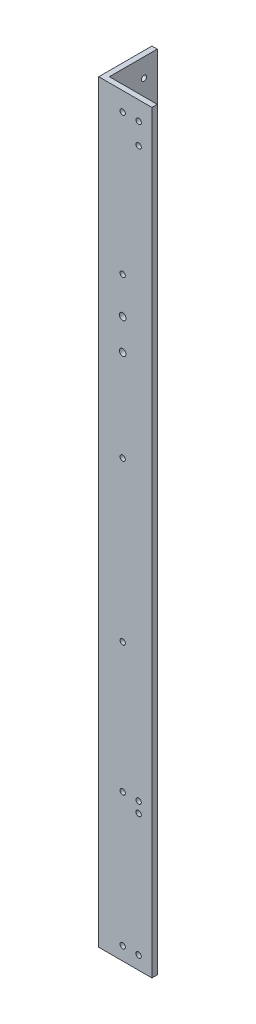
SolidWorks part; units mm, degrees
ref_plane "Front Plane" through (0, 0, 0) normal (0, 0, 1) x (1, 0, 0)
ref_plane "Top Plane" through (0, 0, 0) normal (0, 1, 0) x (1, 0, 0)
ref_plane "Right Plane" through (0, 0, 0) normal (1, 0, 0) x (0, 0, -1)
sketch "Sketch2" plane through (0, 0, 0) normal (0, 1, 0) x (1, 0, 0)
  line L0 (0, 31.75) -> (3.175, 31.75)
  line L1 (3.175, 31.75) -> (3.175, 3.175)
  line L2 (3.175, 3.175) -> (31.75, 3.175)
  line L3 (31.75, 3.175) -> (31.75, 0)
  line L4 (31.75, 0) -> (0, 0)
  line L5 (0, 0) -> (0, 31.75)
  point P9 (1.5875, 31.75)
  point P10 (31.75, 1.5875)
  dimension "D4" = 3.175
  dimension "D1" = 31.75
  dimension "D2" = 31.75
  dimension "D3" = 3.175
extrude "Boss-Extrude1" add sketch "Sketch2" along normal blind 450
sketch "FrontSideHoles-Sketch3" plane through (0, 0, 0) normal (0, 0, 1) x (1, 0, 0)
  line L0 (0, 0) -> (31.75, 0) construction
  line L1 (0, 450) -> (0, 0) construction
  circle A1 centre (23.8125, 81.1125) radius 1.5875
  circle A2 centre (14.2875, 87.4625) radius 1.5875
  circle A3 centre (23.8125, 87.4625) radius 1.5875
  circle A4 centre (14.2875, 438.8875) radius 1.5875
  circle A6 centre (23.8125, 438.8875) radius 1.5875
  circle A7 centre (23.8125, 426.1875) radius 1.5875
  circle A8 centre (14.2875, 333.1776) radius 2
  circle A9 centre (14.2875, 314.6526) radius 2
  circle A10 centre (14.2875, 260) radius 1.5875
  circle A11 centre (14.2875, 165) radius 1.5875
  circle A12 centre (14.2875, 355) radius 1.5875
  circle A13 centre (14.2875, 7.9375) radius 1.5875
  circle A14 centre (23.8125, 7.9375) radius 1.5875
  dimension "D4" = 3.175
  dimension "D15" = 4
  dimension "D8" = 11.1125
  dimension "D11" = 18.525
  dimension "D9" = 314.6526
  dimension "D6" = 165
  dimension "D10" = 95
  dimension "D13" = 95
  dimension "D12" = 7.9375
  dimension "D3" = 9.525
  dimension "D2" = 14.2875
  dimension "D5" = 6.35
  dimension "D14" = 81.1125
  dimension "D7" = 12.7
sketch "LeftSideHoles-Sketch4" plane through (0, 0, 0) normal (-1, 0, 0) x (0, 0, 1)
  line L0 (-31.75, 450) -> (0, 450) construction
  line L1 (0, 450) -> (0, 0) construction
  line L3 (-31.75, 0) -> (0, 0) construction
  circle A0 centre (-23.8125, 81.1125) radius 1.5875
  circle A1 centre (-14.2875, 81.1125) radius 1.5875
  circle A2 centre (-23.8125, 87.4625) radius 1.5875
  circle A4 centre (-23.8125, 438.8875) radius 1.5875
  circle A6 centre (-23.8125, 426.1875) radius 1.5875
  circle A7 centre (-14.2875, 426.1875) radius 1.5875
  circle A8 centre (-23.8125, 327.6026) radius 1.5875
  circle A9 centre (-14.2875, 327.6026) radius 1.5875
  circle A10 centre (-23.8125, 314.9026) radius 1.5875
  circle A11 centre (-14.2875, 314.9026) radius 1.5875
  circle A12 centre (-23.8125, 7.9375) radius 1.5875
  circle A13 centre (-14.2875, 7.9375) radius 1.5875
  circle A14 centre (-14.2875, 165) radius 1.5875
  circle A15 centre (-14.2875, 260) radius 1.5875
  circle A16 centre (-14.2875, 355) radius 1.5875
  dimension "D4" = 3.175
  dimension "D13" = 95
  dimension "D2" = 14.2875
  dimension "D5" = 6.35
  dimension "D7" = 12.7
  dimension "D3" = 81.1125
  dimension "D6" = 11.1125
  dimension "D10" = 7.9375
  dimension "D9" = 12.7
  dimension "D11" = 9.525
  dimension "D8" = 327.6026
  dimension "D12" = 165
  dimension "D14" = 95
extrude "FrontSideHoles-Cut-Extrude1" cut sketch "FrontSideHoles-Sketch3" against normal blind 3.175
extrude "LeftSideHoles-Cut-Extrude2" cut sketch "LeftSideHoles-Sketch4" against normal blind 3.175
equation "\"RailThickness\"= .125in'Spec"
equation "\"VSWidth\"= 1.25in'Spec"
equation "\"VSHeight\"= 1.25in'Spec"
equation "\"VSLength\"= 450mm"
equation "\"HoleOffsetFromEdge\"= \"RailThickness\" * 2.5"
equation "\"HoleOffsetFromSide\"= \"RailThickness\" * 3.5"
equation "\"LegHeight\"= 70mm'Space needed for PSU/Stepper/Electronics"
equation "\"VSBottomSideRailHoleY1FromBottomOfLowerRail\"= \"V1 BottomOfLowerRail\" + \"HoleOffsetFromSide\"'Equals 70.1125"
equation "\"VSSideRailHoleX1FromSide\"= \"HoleOffsetFromSide\" + \"RailThickness\""
equation "\"FasteningHoleDiameter\"= .125in"
equation "\"VSBottomSideRailHoleY2FromY1\"= \"LowerRailHeight\" - \"HoleOffsetFromSide\" - \"HoleOffsetFromEdge\"'Equals 6.35"
equation "\"VSTopSideRailHoleY1FromEdge\"= \"HoleOffsetFromEdge\" + \"RailThickness\""
equation "\"D4@FrontSideHoles-Sketch3\" = \"FasteningHoleDiameter\""
equation "\"D1@Boss-Extrude1\"=\"VSLength\""
equation "\"D4@LeftSideHoles-Sketch4\" = \"FasteningHoleDiameter\""
equation "\"D3@LeftSideHoles-Sketch4\"= \"VSBottomSideRailHoleY1FromBottomOfLowerRail\""
equation "\"D8@FrontSideHoles-Sketch3\" = \"VSTopSideRailHoleY1FromEdge\""
equation "\"D6@LeftSideHoles-Sketch4\" = \"VSTopSideRailHoleY1FromEdge\""
equation "\"VSMidSideRailHoleY1FromV8TopOfMidSideRail\"= \"V8 ToTopOfMidSideRail\" - \"HoleOffsetFromEdge\"'Equals 308.2875"
equation "\"LowerRailHeight\"= 1.00in"
equation "\"D1@Sketch2\"=\"VSHeight\""
equation "\"D2@Sketch2\"=\"VSWidth\""
equation "\"TopRailHeight\"= 1.25in"
equation "\"MidSideRailHeight\"= 1.25in"
equation "\"D10@LeftSideHoles-Sketch4\"=\"HoleOffsetFromEdge\""
equation "\"VSMidSideRailHoleY2FromY1\"= \"MidSideRailHeight\" - \"HoleOffsetFromSide\" - \"HoleOffsetFromEdge\"'Equals 12.7"
equation "\"D9@LeftSideHoles-Sketch4\"=\"VSMidSideRailHoleY2FromY1\""
equation "\"VSSideRailHoleX2FromX1\"= \"VSWidth\" - \"VSSideRailHoleX1FromSide\" - \"HoleOffsetFromEdge\""
equation "\"D11@LeftSideHoles-Sketch4\"=\"VSSideRailHoleX2FromX1\""
equation "\"VSTopSideRailHoleY2FromY1\"= \"TopRailHeight\" - \"VSTopSideRailHoleY1FromEdge\" - \"HoleOffsetFromEdge\"'Equals 12.7"
equation "\"D7@LeftSideHoles-Sketch4\"=\"VSTopSideRailHoleY2FromY1\""
equation "\"BeltTensionerInnerHeight\"= \"20TGT2PulleyWidth\" * 2 + \"1mmSpacer\" * 3"
equation "\"20TGT2PulleyWidth\"= 8.7mm'The STL of the Pulley in the diagram is a bit larger"
equation "\"1mmSpacer\"= 1mm"
equation "\"BeltTensionerHeight\"= \"BeltTensionerInnerHeight\" + \"BeltTensionerUpperLowerWallThickness\" * 2"
equation "\"BeltTensionerUpperLowerWallThickness\"= 7mm"
equation "\"D11@FrontSideHoles-Sketch3\"=\"VSBeltTensionerHoleY2FromY1\""
equation "\"VSBeltTensionerHoleY1FromBottom\"= \"V9 FromBottomGantryPulleyToBottomOfBeltTensioner\" + \"HoleOffsetFromEdge\""
equation "\"VSBeltTensionerHoleY2FromY1\"= \"BeltTensionerHeight\" - \"HoleOffsetFromEdge\" * 2"
equation "\"V1 BottomOfLowerRail\"= \"LegHeight\""
equation "\"StepperShaftLength\"= 24mm'Pulley will be attached to the end"
equation "\"ZAxisLeadScrewLength\"= 200mm"
equation "\"LM8UUHeight\"= 24mm'Spec"
equation "\"V2 ToBedAtTopOfZAxis\"= \"V1 BottomOfLowerRail\" - \"LowerEnclosureThickness\" + \"StepperShaftLength\" + \"ZAxisLeadScrewLength\" - \"LM8UUHeight\" / 2"
equation "\"HotEndToTopOfXAxisGB\"= 63.315144mm'Measured from the100.Should be 63.315144"
equation "\"TopOfGBToBottomOfLinearRail\"= \"LinearGBWidth\" / 2 + \"LinearRailWidth\" / 2"
equation "\"LinearGBWidth\"= 27mm'Spec"
equation "\"V5 ToBottomOfXAxisLinearRail\"= \"V4 ToTopOfBuildPlate/HotEndTip\" + \"HotEndToTopOfXAxisGB\" - \"TopOfGBToBottomOfLinearRail\""
equation "\"LinearRailWidth\"= 12mm'Spec"
equation "\"V6 ToBottomOfGantryPulley\"= \"V5 ToBottomOfXAxisLinearRail\" - \"DistanceFromGABTopToLowerPulley\""
equation "\"GABUpperHeight\"= 6mm"
equation "\"GABMidWallHeight\"= 28mm'Must equal 28 or changes alignment"
equation "\"GABMidShortRiserHeight\"= \"GABMidWallHeight\" / 2 - \"20TGT2PulleyWidth\"'Equals 5.3"
equation "\"GABRiserBossOffset\"= 0.8mm'Aligns Pulleys"
equation "\"DistanceFromGABTopToLowerPulley\"= \"GABUpperHeight\" + \"GABMidWallHeight\" - \"GABMidShortRiserHeight\" + \"GABRiserBossOffset\" / 2"
equation "\"V7 ToTopOfMidBackRail\"= \"V6 ToBottomOfGantryPulley\" + \"StepperShaftLength\""
equation "\"D8@LeftSideHoles-Sketch4\"= \"VSMidSideRailHoleY1FromV8TopOfMidSideRail\""
equation "\"BedToBuildPlateStandoffLength\"= 15mm"
equation "\"BuildPlateHeight\"= 8mm'Spec"
equation "\"V4 ToTopOfBuildPlate/HotEndTip\"= \"V2 ToBedAtTopOfZAxis\" + \"BedToBuildPlateStandoffLength\" + \"BuildPlateHeight\""
equation "\"D9@FrontSideHoles-Sketch3\"=\"VSBeltTensionerHoleY1FromBottom\""
equation "\"V8 ToTopOfMidSideRail\"= \"V7 ToTopOfMidBackRail\" - \"RailThickness\""
equation "\"V9 FromBottomGantryPulleyToBottomOfBeltTensioner\"= \"V6 ToBottomOfGantryPulley\" - \"BeltTensionerUpperLowerWallThickness\" - \"1mmSpacer\""
equation "\"BeltTensionerMountingHoleOffsetFromEdge\"= \"HoleOffsetFromEdge\""
equation "\"VSBeltTensionerXMountingHoleOffsetFromSide\"= \"BeltTensionerMountingHoleOffsetFromEdge\" + \"RailThickness\" * 2"
equation "\"VSEnclosureOffsets\"= ( \"VSLength\" - \"LegHeight\" ) / 4"
equation "\"D6@FrontSideHoles-Sketch3\"=\"LegHeight\" + \"VSEnclosureOffsets\""
equation "\"D10@FrontSideHoles-Sketch3\"=\"VSEnclosureOffsets\""
equation "\"D13@FrontSideHoles-Sketch3\"=\"VSEnclosureOffsets\""
equation "\"D12@FrontSideHoles-Sketch3\"=\"HoleOffsetFromEdge\""
equation "\"D13@LeftSideHoles-Sketch4\"=\"VSEnclosureOffsets\""
equation "\"D14@LeftSideHoles-Sketch4\"=\"VSEnclosureOffsets\""
equation "\"D12@LeftSideHoles-Sketch4\"=\"LegHeight\" + \"VSEnclosureOffsets\""
equation "\"D3@FrontSideHoles-Sketch3\"=\"VSSideRailHoleX2FromX1\""
equation "\"D2@FrontSideHoles-Sketch3\"=\"VSSideRailHoleX1FromSide\""
equation "\"D5@FrontSideHoles-Sketch3\"=\"VSBottomSideRailHoleY2FromY1\""
equation "\"D14@FrontSideHoles-Sketch3\"=\"VSBottomSideRailHoleY1FromBottomOfLowerRail\""
equation "\"D7@FrontSideHoles-Sketch3\"=\"VSTopSideRailHoleY2FromY1\""
equation "\"D5@LeftSideHoles-Sketch4\"=\"VSBottomSideRailHoleY2FromY1\""
equation "\"BeltTensionerMountingHoleDiameter\"= 4.0mm"
equation "\"D15@FrontSideHoles-Sketch3\"=\"BeltTensionerMountingHoleDiameter\""
equation "\"LowerEnclosureThickness\"= 5mm"
